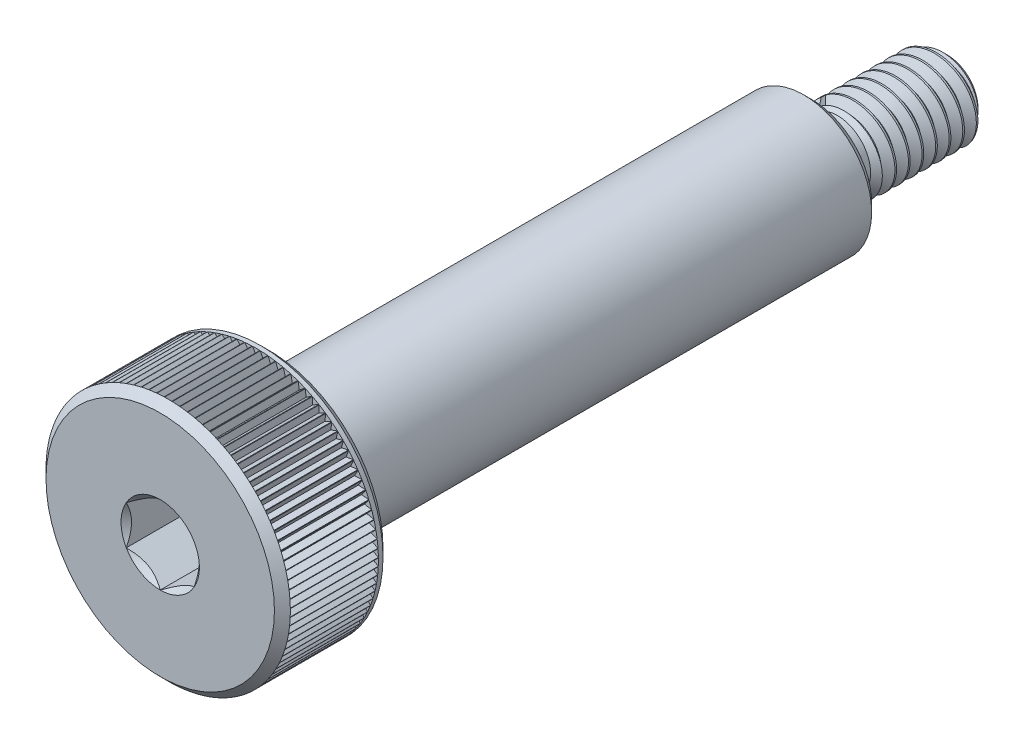
SolidWorks part; units mm, degrees
ref_plane "Front Plane" through (0, 0, 0) normal (0, 0, 1) x (1, 0, 0)
ref_plane "Top Plane" through (0, 0, 0) normal (0, 1, 0) x (1, 0, 0)
ref_plane "Right Plane" through (0, 0, 0) normal (1, 0, 0) x (0, 0, -1)
sketch "Sketch1" plane through (0, 0, 0) normal (1, 0, 0) x (0, 0, -1)
  line L0 (-14.5, 0) -> (14.5, 0) construction
  line L1 (-14.5, -4.5) -> (-14.5, 4.5) construction
  line L2 (-14.5, 4.5) -> (-10.5, 4.5) construction
  line L3 (-10.5, 4.5) -> (-10.5, 2.297) construction
  line L4 (-10.5, 2.297) -> (-9.992, 2.297) construction
  line L5 (-9.992, 2.297) -> (-9.789, 2.5) construction
  line L6 (-9.789, 2.5) -> (9.5, 2.5) construction
  line L7 (14.4688, 1.5541) -> (14.7188, 1.1211) construction
  line L8 (14.7188, 1.1211) -> (14.9688, 1.5541) construction
  line L9 (14.5, -1.5) -> (14.5, 1.5) construction
  line L10 (9.5, 2.5) -> (14.5, 2.5) construction
  line L11 (14.9688, 1.5541) -> (14.4688, 1.5541) construction
  line L12 (14.7188, 1.5541) -> (14.7188, 1.5) construction
  line L13 (14.7188, 1.1211) -> (14.7188, 1.1752) construction
  line L14 (14.75, 1.1752) -> (14.6875, 1.1752) construction
  line L15 (14.9375, 1.5) -> (14.5, 1.5) construction
  line L16 (14.7188, 1.5271) -> (14.9531, 1.5271) construction
  line L17 (14.7188, 1.5271) -> (14.4844, 1.5271) construction
  line L18 (-14.5, 4.2075) -> (-14.2075, 4.5) construction
  line L19 (-10.7925, 4.5) -> (-10.5, 4.2075) construction
  line L20 (14.5, 1.5) -> (9.5, 1.5) construction
  line L21 (14.125, 1.5) -> (14.5, 1.125) construction
  line L22 (10.7313, 1.5) -> (10.45, 1.2187) construction
  line L23 (10.45, 1.2187) -> (9.6406, 1.2187) construction
  line L24 (9.5, 1.5) -> (9.5, 1.3594) construction
  line L25 (-12.5, 1.25) -> (-12.5, -1.25) construction
  line L26 (-12.5, -1.25) -> (-14.5, -1.25) construction
  line L27 (-12.5, 1.25) -> (-14.5, 1.25) construction
  line L28 (-14.2075, 0) -> (-10.9633, 0) construction
  arc A0 (9.5, 1.3594) -> (9.6406, 1.2187) centre (9.6406, 1.3594) ccw construction
  point P4 (0, 0)
  point P7 (-14.5, 0)
  point P18 (14.5, 0)
  point P25 (12.75, -1.5)
  point P38 (-12.5, 4.5)
  point P45 (-12.5, 0)
  point P46 (10.5906, 1.3594)
  point P48 (-9.992, 0)
  point P51 (-12.5, 0)
  point P52 (9.5, 0)
  point P53 (-7.3, 0)
  dimension "Head Diameter" = 9
  dimension "Head Height" = 4
  dimension "Thread Diameter" = 3
  dimension "Shoulder Diameter" = 5
  dimension "Thread Length" = 5
  dimension "D1" = 0.508
  dimension "D2" = 135
  dimension "D3" = 0.203
  dimension "Shoulder Length" = 20
  dimension "Thread Pitch" = 0.5
  dimension "D4" = 0.0625
  dimension "D5" = 1.75
  dimension "D6" = 0.2925
  dimension "D7" = 0.375
  dimension "D8" = 2.4375
  dimension "D9" = 0.95
  dimension "Drive Size" = 2.5
  dimension "Knurling Length" = 3.2443
  dimension "D10" = 7.2
sketch "Sketch3" plane through (0, 0, 0) normal (1, 0, 0) x (0, 0, -1)
  line L0 (-14.5, 0) -> (-14.5, 4.2075)
  line L1 (-14.5, -4.5) -> (-14.5, 4.5) construction
  line L2 (-14.5, 4.2075) -> (-14.2075, 4.5)
  line L3 (-14.2075, 4.5) -> (-10.7925, 4.5)
  line L4 (-10.7925, 4.5) -> (-10.5, 4.2075)
  line L5 (-10.5, 4.2075) -> (-10.5, 2.297)
  line L6 (-10.5, 2.297) -> (-9.992, 2.297)
  line L7 (-9.992, 2.297) -> (-9.789, 2.5)
  line L8 (-9.789, 2.5) -> (9.5, 2.5)
  line L9 (9.5, 2.5) -> (9.5, 1.3594)
  line L10 (9.6406, 1.2187) -> (10.45, 1.2187)
  line L11 (10.45, 1.2187) -> (10.7313, 1.5)
  line L12 (10.7313, 1.5) -> (14.125, 1.5)
  line L13 (14.125, 1.5) -> (14.5, 1.125)
  line L14 (14.5, 1.125) -> (14.5, 0)
  line L15 (14.5, 0) -> (-14.5, 0)
  arc A0 (9.5, 1.3594) -> (9.6406, 1.2187) centre (9.6406, 1.3594) ccw construction
  arc A1 (9.5, 1.3594) -> (9.6406, 1.2187) centre (9.6406, 1.3594) ccw
revolve "Revolve1" add sketch "Sketch3" angle 360 about L0
sketch "Sketch4" plane through (0, 0, 0) normal (0, 0, 1) x (1, 0, 0)
  line L0 (0, -4.5) -> (0, 4.5) construction
  line L1 (0, 1.4434) -> (-1.25, 0.7217)
  line L2 (-1.25, 0.7217) -> (-1.25, -0.7217)
  line L3 (-1.25, -0.7217) -> (0, -1.4434)
  line L4 (0, -1.4434) -> (1.25, -0.7217)
  line L5 (1.25, -0.7217) -> (1.25, 0.7217)
  line L6 (1.25, 0.7217) -> (0, 1.4434)
  circle A0 centre (0, 0) radius 1.25 construction
extrude "Cut-Extrude1" cut sketch "Sketch4" against normal up to vertex (-12.5 mm away) from vertex up to point (0, 0, 12.5) starting at point (0, 0, 14.5)
sketch "Sketch5" plane through (0, 0, 0) normal (0, 0, 1) x (1, 0, 0)
  line L0 (0, -4.5) -> (0, 4.5) construction
  circle A0 centre (0, 0) radius 1.4434
extrude "Cut-Extrude2" cut sketch "Sketch5" against normal up to vertex (-12.5 mm away) draft 45 from vertex up to point (0, 0, 12.5) starting at point (0, 0, 14.5)
chamfer "Chamfer1" distance 0.2925 angle 45 1 edges at (2.5, 0, -9.5)
sketch "Sketch6" plane through (0, 0, -14.5) normal (0, 0, -1) x (-1, 0, 0)
  circle A0 centre (0, 0) radius 1.5
curve "Helix/Spiral1" pitch 0.5 height 4.05 radius 1.5 centre (0, 0, -14.5) axis (0, 0, 1) start towards (0, 1, 0)
sketch "Sketch7" plane through (0, 0, 0) normal (1, 0, 0) x (0, 0, -1)
  line L0 (14.4844, 1.5271) -> (14.6875, 1.1752)
  line L1 (14.6875, 1.1752) -> (14.75, 1.1752)
  line L2 (14.75, 1.1752) -> (14.9531, 1.5271)
  line L3 (14.9531, 1.5271) -> (14.4844, 1.5271)
sweep "Cut-Sweep1" cut profiles "Sketch7" path "Helix/Spiral1"
sketch "Sketch8" plane through (0, 0, 0) normal (0, 0, 1) x (1, 0, 0)
  line L0 (0, 4.5) -> (0, 0) construction
  line L1 (-0.1351, 4.5) -> (0.1351, 4.5)
  line L2 (0.1351, 4.5) -> (0, 4.266)
  line L3 (0, 4.266) -> (-0.1351, 4.5)
  line L4 (-0.1351, 4.5) -> (0, 0) construction
  line L5 (0, 0) -> (0.1351, 4.5) construction
  circle A0 centre (0, 0) radius 4.266 construction
  point P8 (0, 4.5)
  dimension "D1" = 0.234
  dimension "D2" = 3.439
extrude "Cut-Extrude3" cut sketch "Sketch8" against normal up to vertex (-10.9633 mm away) from vertex up to point (0, 0, 10.9633) starting at point (0, 0, 14.2075)
pattern_circular "CirPattern1" count 99 over 360 about axis through (0, 0, 14.5) along (0, 0, -1) of "Cut-Extrude3"
equation "\"D4@Sketch1\"=\"Thread Pitch@Sketch1\"/8"
equation "\"D5@Sketch1\"=\"Thread Pitch@Sketch1\"*3.5"
equation "\"D6@Sketch1\"=\"Head Diameter@Sketch1\"*.0325"
equation "\"D7@Sketch1\"=\"Thread Pitch@Sketch1\"*.75"
equation "\"D1@Chamfer1\"=\"D6@Sketch1\""
equation "\"D4@Helix/Spiral1\"=\"Thread Pitch@Sketch1\""
equation "\"D3@Helix/Spiral1\" = \"Thread Length@Sketch1\" - \"D9@Sketch1\""
equation "\"D1@Sketch8\"=\"D6@Sketch1\"*.8"
equation "\"D1@CirPattern1\"=(360/\"D2@Sketch8\")-6"
equation "\"D9@Sketch1\"  = \"Thread Length@Sketch1\"*.2"
equation "\"D8@Sketch1\"=\"Thread Diameter@Sketch1\"*.65"
equation "\"D10@Sketch1\"=\"Head Diameter@Sketch1\"*.8"
